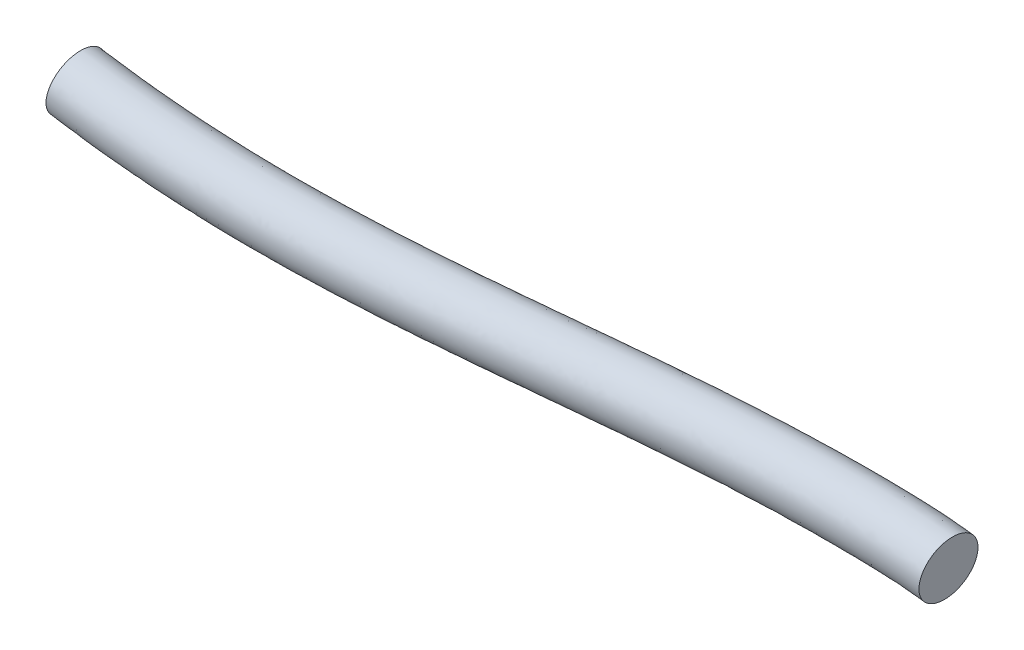
SolidWorks part; units mm, degrees
ref_plane "Front Plane" through (0, 0, 0) normal (0, 0, 1) x (1, 0, 0)
ref_plane "Top Plane" through (0, 0, 0) normal (0, 1, 0) x (1, 0, 0)
ref_plane "Right Plane" through (0, 0, 0) normal (1, 0, 0) x (0, 0, -1)
sketch "Sketch1" plane through (0, 0, 0) normal (0, 0, 1) x (1, 0, 0)
  spline S0 degree 3 poles (-45.0249, 7.078) (-26.6796, 4.0351) (-6.8897, 9.1168) (13.0068, 8.2854) (14.5423, 8.0781) knots 0 0 0 0 0.922189 1 1 1 1
sweep "Sweep1" add path "Sketch1" circular profile diameter 4 parameters "D3"=4
